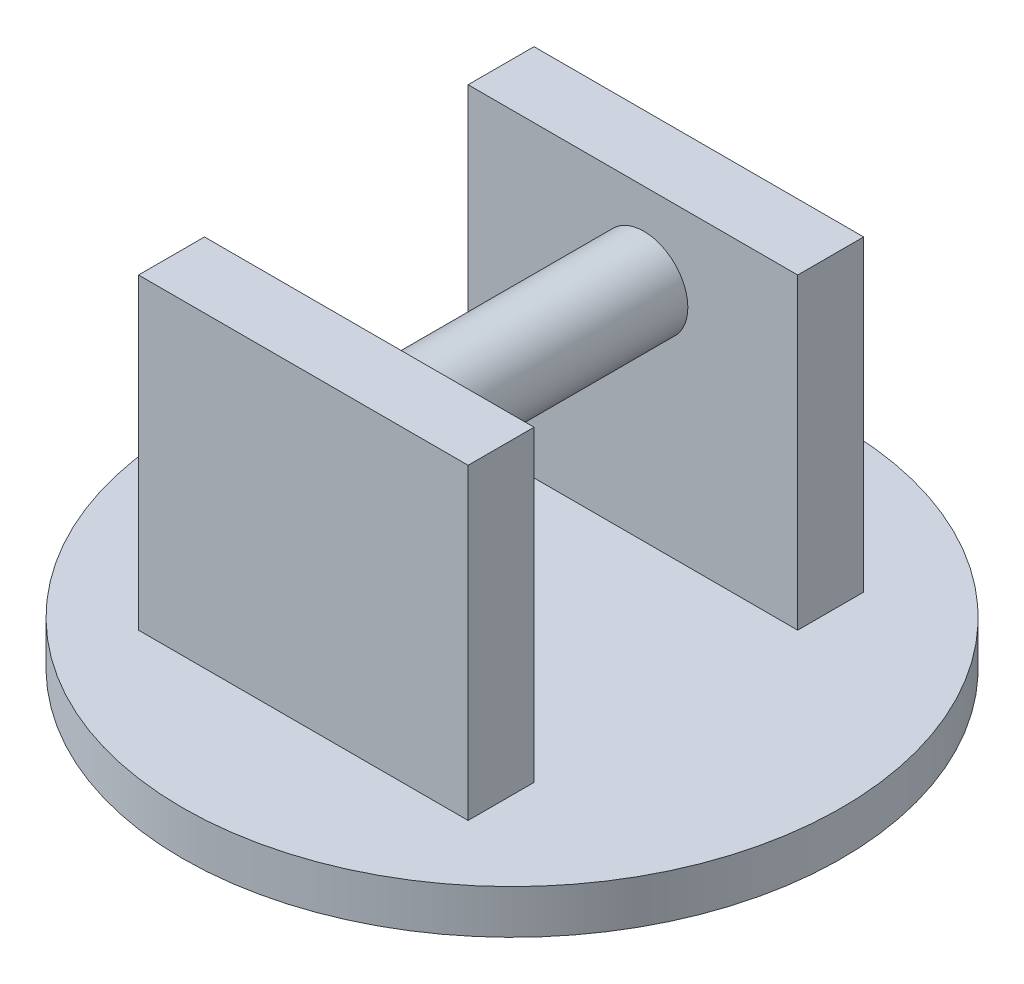
SolidWorks part; units mm, degrees
ref_plane "Front Plane" through (0, 0, 0) normal (0, 0, 1) x (1, 0, 0)
ref_plane "Top Plane" through (0, 0, 0) normal (0, 1, 0) x (1, 0, 0)
ref_plane "Right Plane" through (0, 0, 0) normal (1, 0, 0) x (0, 0, -1)
sketch "Sketch1" plane through (0, 0, 0) normal (0, 1, 0) x (1, 0, 0)
  circle A0 centre (0, 0) radius 75
extrude "Boss-Extrude1" add sketch "Sketch1" along normal blind 10
sketch "Sketch2" plane through (0, 0, 0) normal (0, -1, 0) x (-1, 0, 0)
  circle A0 centre (0, 0) radius 15
extrude "Boss-Extrude2" add sketch "Sketch2" along normal blind 25
sketch "Sketch3" plane through (0, 10, 0) normal (0, 1, 0) x (1, 0, 0)
  line L1 (-40, -45) -> (35, -45)
  line L2 (-40, -45) -> (-40, -30)
  line L3 (-40, -30) -> (35, -30)
  line L4 (35, -45) -> (35, -30)
  line L5 (-40, 30) -> (35, 30)
  line L6 (-40, 30) -> (-40, 45)
  line L7 (-40, 45) -> (35, 45)
  line L8 (35, 30) -> (35, 45)
  dimension "D1" = 75
  dimension "D2" = 15
  dimension "D3" = 15
  dimension "D4" = 75
  dimension "D5" = 30
  dimension "D6" = 30
  dimension "D7" = 50
  dimension "D8" = 50
extrude "Boss-Extrude3" add sketch "Sketch3" along normal blind 70
sketch "Sketch4" plane through (0, 0, 45) normal (0, 0, 1) x (1, 0, 0)
  circle A0 centre (0, 61.1108) radius 10
extrude "Boss-Extrude4" add sketch "Sketch4" against normal blind 90
